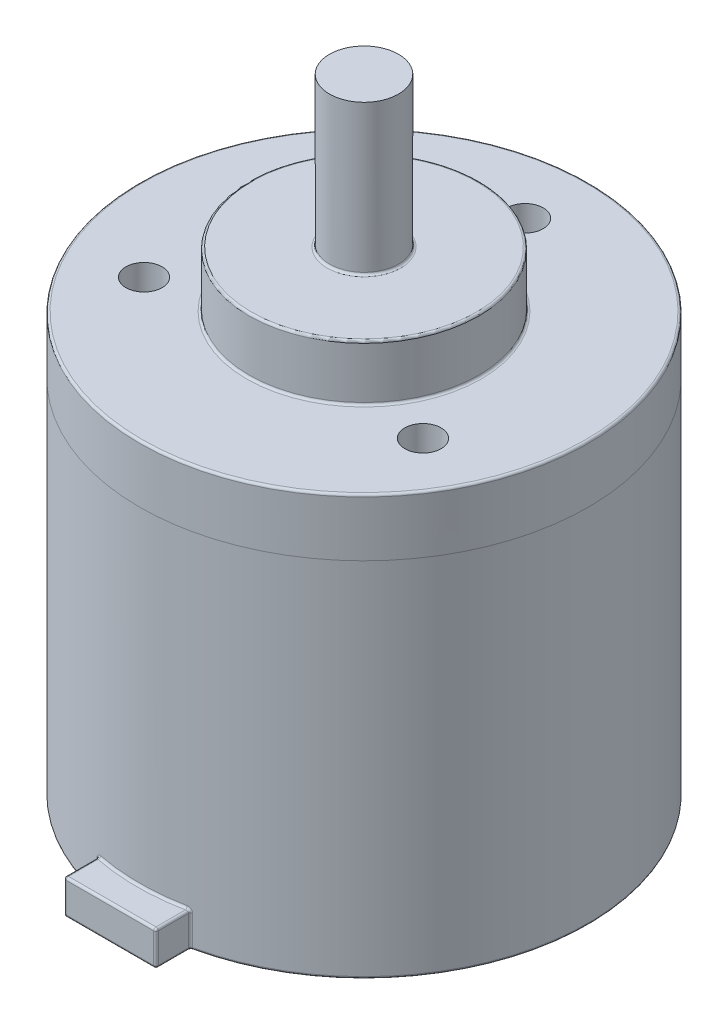
SolidWorks part; units mm, degrees
ref_plane "Front Plane" through (0, 0, 0) normal (0, 0, 1) x (1, 0, 0)
ref_plane "Top Plane" through (0, 0, 0) normal (0, 1, 0) x (1, 0, 0)
ref_plane "Right Plane" through (0, 0, 0) normal (1, 0, 0) x (0, 0, -1)
sketch "Sketch1" plane through (0, 0, 0) normal (0, 1, 0) x (1, 0, 0)
  circle A0 centre (0, 0) radius 19.5
  dimension "D1" = 39
extrude "Boss-Extrude1" add sketch "Sketch1" along normal blind 36.5
sketch "Sketch2" plane through (0, 36.5, 0) normal (0, 1, 0) x (1, 0, 0)
  circle A0 centre (0, 0) radius 10
  dimension "D1" = 20
extrude "Boss-Extrude2" add sketch "Sketch2" along normal blind 4.85
extrude "Boss-Extrude3" add sketch "Sketch2<2>" along normal blind 4.85
sketch "Sketch2<2>" plane through (0, 36.5, 0) normal (0, 1, 0) x (1, 0, 0) same geometry as "Sketch2"
sketch "Sketch5" plane through (0, 41.35, 0) normal (0, 1, 0) x (1, 0, 0)
  circle A0 centre (0, 0) radius 3
  dimension "D1" = 6
extrude "Boss-Extrude4" add sketch "Sketch5" along normal blind 13
sketch "Sketch11" plane through (0, 0, 0) normal (0, 0, 1) x (1, 0, 0)
  line L0 (-24.9932, 31.5) -> (25.4595, 31.5)
  line L1 (19.5, 36.5) -> (-19.5, 36.5) construction
  dimension "D1" = 5
split line "Split Line12"
hole_wizard "Tap Drill for M3 Helicoil1" positions "Sketch13" profile "Sketch14" hole size "M3x0.5" standard "ANSI Metric"
sketch "Sketch13" plane through (0, 36.5, 0) normal (0, 1, 0) x (1, 0, 0)
  circle A0 centre (0, 0) radius 19.5 construction
  point P0 (0, 14)
  dimension "D1" = 14
sketch "Sketch14" plane through (0, 36.5, -14) normal (1, 0, 0) x (0, 0, 1)
  line L0 (0, 0) -> (0, 5.9464)
  line L1 (0, 5.9464) -> (1.575, 5)
  line L2 (1.575, 5) -> (1.575, 0)
  line L5 (1.575, 0) -> (0, 0)
  line L10 (0, 5.9464) -> (-1.575, 5) construction
  line L11 (0, -6.35) -> (0, 107.95) construction
  dimension "Hole Dia." = 3.15
  dimension "Hole Depth" = 5
  dimension "Drill Angle" = 118
pattern_circular "CirPattern1" count 3 over 360 about axis through (0, 36.5, 0) along (0, 1, 0) of "Tap Drill for M3 Helicoil1"
sketch "Sketch15" plane through (0, 0, 0) normal (0, -1, 0) x (1, 0, 0)
  line L2 (-4, 19.0853) -> (-4, 22.0853)
  line L3 (-4, 22.0853) -> (4, 22.0853)
  line L4 (4, 19.0853) -> (4, 22.0853)
  line L5 (0, 19.5) -> (4, 22.0853) construction
  line L6 (-4, 22.0853) -> (0, 19.5) construction
  circle A0 centre (0, 0) radius 19.5 construction
  arc A1 (4, 19.0853) -> (-4, 19.0853) centre (0, 0) ccw
  point P0 (0, 19.5)
  dimension "D1" = 8
  dimension "D2" = 3
extrude "Boss-Extrude5" add sketch "Sketch15" against normal blind 3
fillet "Fillet1" radius 0.2 12 edges at (0, 3, 19.5) (0, 0, -19.5) (4, 3, 20.5853) (4, 1.5, 19.0853) (4, 0, 20.5853) (-4, 1.5, 19.0853) (-4, 3, 20.5853) (-4, 0, 20.5853) (-4, 1.5, 22.0853) (0, 3, 22.0853) (4, 1.5, 22.0853) (0, 0, 22.0853)
fillet "Fillet2" radius 0.2 4 edges at (0, 41.35, 3) (0, 41.35, 10) (0, 36.5, 10) (0, 36.5, 19.5)
